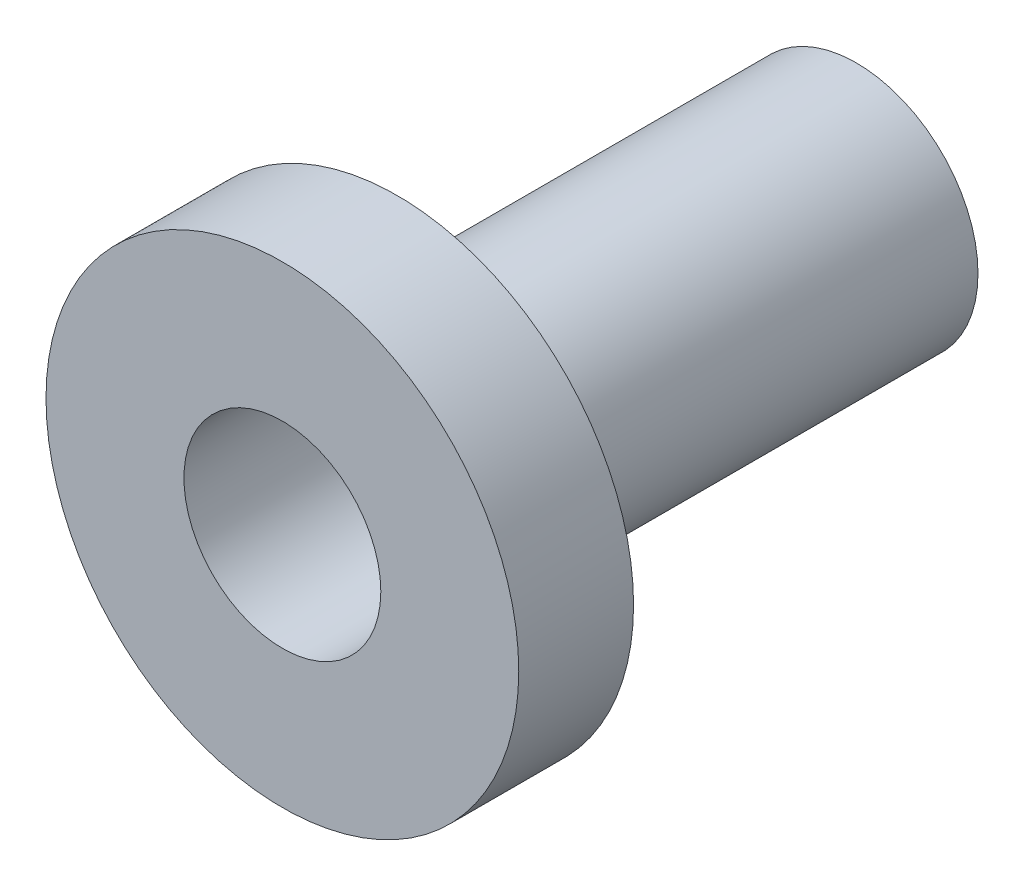
SolidWorks part; units mm, degrees
ref_plane "Front Plane" through (0, 0, 0) normal (0, 0, 1) x (1, 0, 0)
ref_plane "Top Plane" through (0, 0, 0) normal (0, 1, 0) x (1, 0, 0)
ref_plane "Right Plane" through (0, 0, 0) normal (1, 0, 0) x (0, 0, -1)
sketch "Sketch1" plane through (0, 0, 0) normal (0, 0, 1) x (1, 0, 0)
  circle A0 centre (0, 0) radius 18
extrude "Boss-Extrude1" add sketch "Sketch1" along normal blind 85
sketch "Sketch2" plane through (0, 0, 85) normal (0, 0, 1) x (1, 0, 0)
  circle A0 centre (0, 0) radius 14.576
extrude "Cut-Extrude1" cut sketch "Sketch2" against normal blind 60
sketch "Sketch3" plane through (0, 0, 0) normal (0, 0, -1) x (-1, 0, 0)
  circle A0 centre (0, 0) radius 4.3644
extrude "Cut-Extrude2" cut sketch "Sketch3" against normal blind 60
sketch "Sketch4" plane through (0, 0, 85) normal (0, 0, 1) x (1, 0, 0)
  circle A0 centre (0, 0) radius 14.576
  circle A1 centre (0, 0) radius 35
extrude "Boss-Extrude2" add sketch "Sketch4" against normal blind 17
